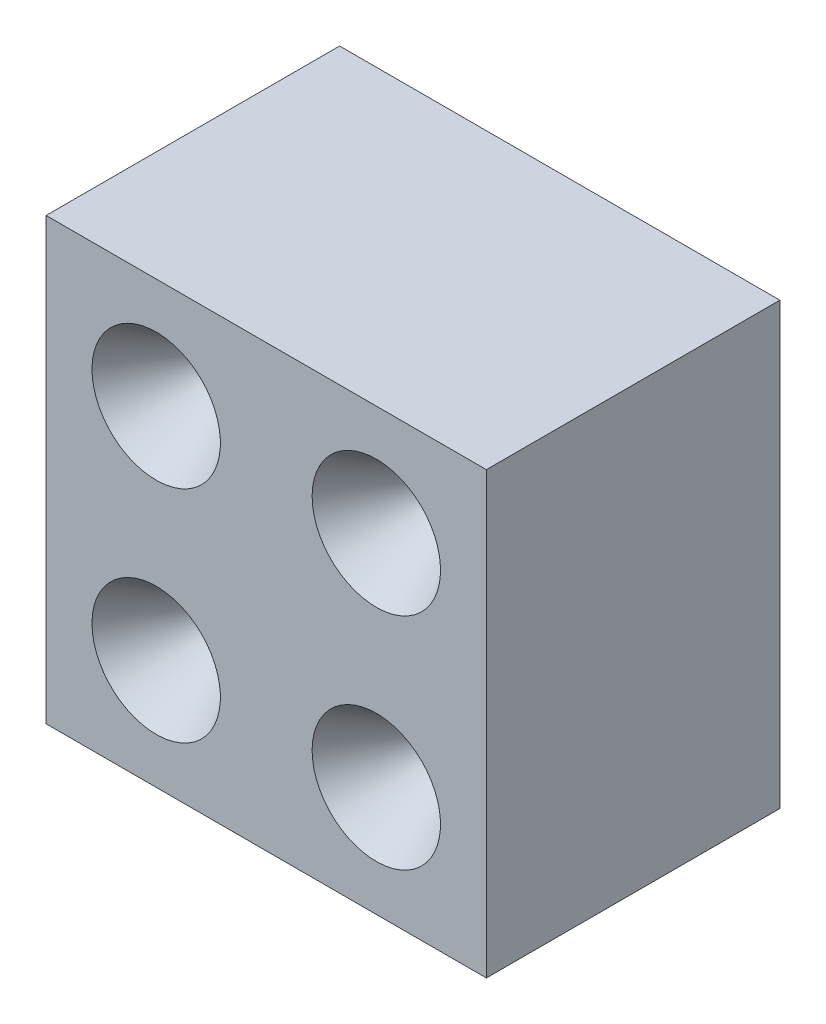
SolidWorks part; units mm, degrees
ref_plane "Front Plane" through (0, 0, 0) normal (0, 0, 1) x (1, 0, 0)
ref_plane "Top Plane" through (0, 0, 0) normal (0, 1, 0) x (1, 0, 0)
ref_plane "Right Plane" through (0, 0, 0) normal (1, 0, 0) x (0, 0, -1)
sketch "Sketch1" plane through (0, 0, 0) normal (0, 0, 1) x (1, 0, 0)
  line L1 (0, 0) -> (3048, 0)
  line L2 (0, 0) -> (0, 3048)
  line L3 (0, 3048) -> (3048, 3048)
  line L4 (3048, 0) -> (3048, 3048)
  dimension "D1" = 3048
  dimension "D2" = 3048
extrude "Boss-Extrude1" add sketch "Sketch1" along normal blind 2032
ref_plane "Plane1" through (0, 0, 1524) normal (0, 0, 1) x (1, 0, 0)
sketch "Sketch2" plane through (0, 0, 2032) normal (0, 0, 1) x (1, 0, 0)
  line L0 (0, 3048) -> (0, 0) construction
  line L1 (3048, 3048) -> (0, 3048) construction
  circle A0 centre (762, 2286) radius 444.5
  point P3 (762, 2286)
  dimension "D1" = 889
  dimension "D2" = 762
  dimension "D3" = 762
sketch "Sketch3" plane through (0, 0, 1524) normal (0, 0, 1) x (1, 0, 0)
  circle A0 centre (762, 2286) radius 127
  dimension "D1" = 254
loft "Cut-Loft1" cut profiles "Sketch2", "Sketch3" connector at (1205.53, 2256.6504, 2032) connector at (885.8457, 2314.1292, 1524)
pattern_linear "LPattern1" count 2 spacing 1524 along (1, 0, 0) count 2 spacing 1524 along (0, -1, 0) of "Cut-Loft1"
sketch "Sketch5" [suppressed] plane through (0, 0, 0) normal (0, 0, -1) x (-1, 0, 0)
  line L0 (0, 3048) -> (0, 0) construction
  line L1 (-3048, 3048) -> (0, 3048) construction
  circle A0 centre (-508, 2540) radius 444.5
  dimension "D1" = 508
  dimension "D2" = 508
ref_plane "Plane2" [suppressed] through (0, 0, 508) normal (0, 0, -1) x (-1, 0, 0)
sketch "Sketch6" [suppressed] plane through (0, 0, 508) normal (0, 0, -1) x (-1, 0, 0)
  circle A0 centre (-508, 2540) radius 127
  dimension "D1" = 254
loft "Cut-Loft2" [suppressed] cut profiles "Sketch5", "Sketch6"
pattern_linear "LPattern2" [suppressed] count 3 spacing 1016 count 3 spacing 1016 of bodies 107
